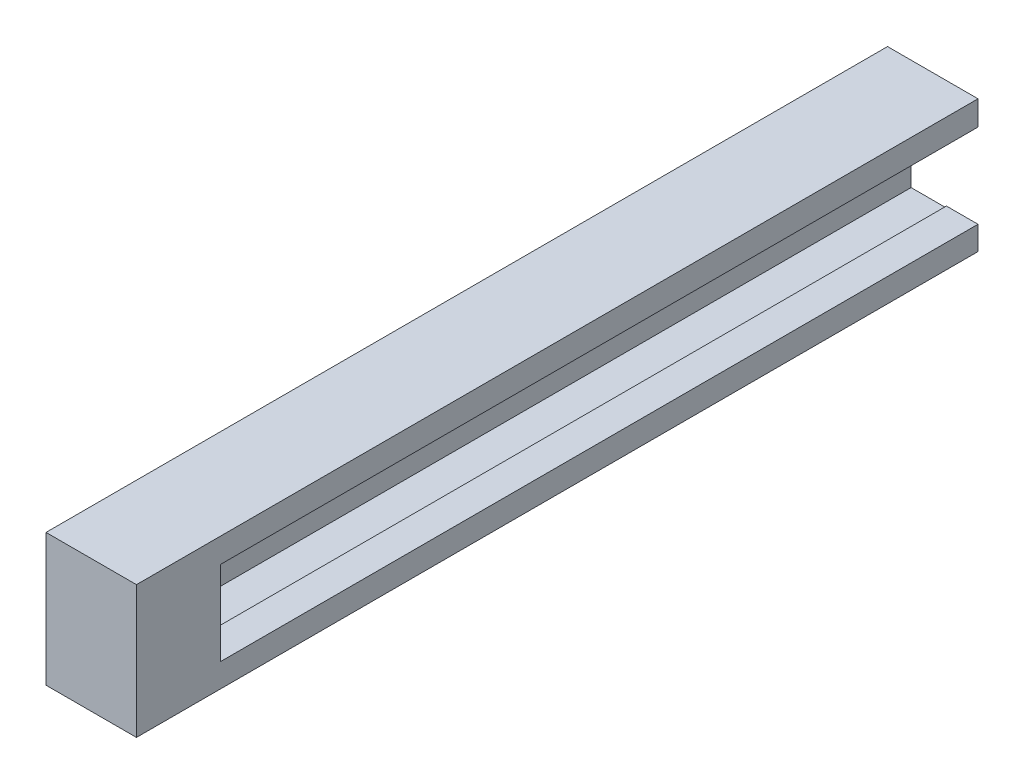
SolidWorks part; units mm, degrees
ref_plane "Front Plane" through (0, 0, 0) normal (0, 0, 1) x (1, 0, 0)
ref_plane "Top Plane" through (0, 0, 0) normal (0, 1, 0) x (1, 0, 0)
ref_plane "Right Plane" through (0, 0, 0) normal (1, 0, 0) x (0, 0, -1)
sketch "Sketch2" plane through (0, 0, 0) normal (0, 0, 1) x (1, 0, 0)
  line L0 (16.75, 6) -> (13, 6) construction
  line L1 (9, 6) -> (13, 6) construction
  line L2 (9, 8.5) -> (9, 6) construction
  line L3 (5, 8.5) -> (9, 8.5) construction
  line L4 (5, 13.5) -> (9, 13.5) construction
  line L5 (9, 16) -> (9, 13.5) construction
  line L6 (9, 16) -> (13, 16) construction
  line L7 (16.75, 16) -> (13, 16) construction
  line L8 (16.75, 6) -> (13, 6)
  line L9 (9, 6) -> (13, 6)
  line L10 (9, 8.5) -> (9, 6)
  line L11 (5, 8.5) -> (9, 8.5)
  line L12 (5, 13.5) -> (9, 13.5)
  line L13 (9, 16) -> (9, 13.5)
  line L14 (9, 16) -> (13, 16)
  line L15 (16.75, 16) -> (13, 16)
  line L16 (16.75, 26) -> (13, 26)
  line L17 (-1, 26) -> (13, 26)
  line L18 (-1, 26) -> (-1, 21.5)
  line L19 (-1, 21.5) -> (-1, 21.5)
  line L20 (5, 13.8) -> (8.7, 13.8)
  line L21 (8.7, 16.3) -> (8.7, 13.8)
  line L22 (8.7, 16.3) -> (13, 16.3)
  line L23 (16.75, 16.3) -> (13, 16.3)
  line L24 (5, 8.3) -> (8.8, 8.3)
  line L25 (8.8, 8.3) -> (8.8, 5.8)
  line L26 (8.8, 5.8) -> (13, 5.8)
  line L27 (16.75, 5.8) -> (13, 5.8)
  line L28 (13, 16.3) -> (13, 16)
  line L29 (13, 5.8) -> (13, 6)
  line L30 (16.75, 5.8) -> (16.75, 6)
  line L31 (16.75, 16.3) -> (16.75, 16)
  line L32 (6, 13.5) -> (6, 13.8)
  line L33 (6, 8.5) -> (6, 8.3)
  line L34 (5, 20) -> (5, 13.5) construction
  line L36 (16.75, 16.3) -> (8.7, 16.3)
  line L37 (16.75, 16.3) -> (16.75, 18.9132)
  line L38 (16.75, 18.9132) -> (8.7, 18.9132)
  line L39 (8.7, 16.3) -> (8.7, 18.9132)
  line L40 (8.7, 18.9132) -> (6, 18.9132)
  line L41 (8.7, 18.9132) -> (8.7, 13.8)
  line L42 (8.7, 13.8) -> (6, 13.8)
  line L43 (6, 18.9132) -> (6, 13.8)
  line L44 (16.75, 5.8) -> (8.8, 5.8)
  line L45 (16.75, 5.8) -> (16.75, 3.1868)
  line L46 (16.75, 3.1868) -> (8.8, 3.1868)
  line L47 (8.8, 5.8) -> (8.8, 3.1868)
  line L48 (8.8, 3.1868) -> (6, 3.1868)
  line L49 (8.8, 3.1868) -> (8.8, 8.3)
  line L50 (8.8, 8.3) -> (6, 8.3)
  line L51 (6, 3.1868) -> (6, 8.3)
  dimension "D4" = 1
  dimension "D1" = 10
  dimension "D2" = 0.3
  dimension "D3" = 0.2
extrude "Boss-Extrude3" add sketch "Sketch2" along normal blind 90 contours L31 L23 L28 L15 | L39 L22 L23 L37 L38 | L40 L43 L20 L21 L39 | L51 L48 L47 L25 L24 | L26 L47 L46 L45 L27 | L27 L30 L8 L29 region at (14.875, 5.9, 0) region at (12.775, 4.4934, 0) region at (7.4, 5.7434, 0) region at (7.35, 16.3566, 0) region at (14.875, 16.15, 0) region at (12.725, 17.6066, 0)
sketch "Sketch3" plane through (0, 0, 90) normal (0, 0, 1) x (1, 0, 0)
  line L0 (6, 8.3) -> (6, 3.1868) construction
  line L1 (6, 3.1868) -> (16.75, 3.1868) construction
  line L2 (16.75, 3.1868) -> (16.75, 6) construction
  line L3 (16.75, 6) -> (13, 6) construction
  line L4 (13, 6) -> (13, 5.8) construction
  line L5 (13, 5.8) -> (8.8, 5.8) construction
  line L6 (8.8, 5.8) -> (8.8, 8.3) construction
  line L7 (8.8, 8.3) -> (6, 8.3) construction
  line L8 (16.75, 16) -> (16.75, 18.9132)
  line L9 (16.75, 18.9132) -> (6, 18.9132)
  line L10 (6, 18.9132) -> (6, 13.8)
  line L11 (6, 13.8) -> (8.7, 13.8)
  line L12 (8.7, 13.8) -> (8.7, 16.3)
  line L13 (8.7, 16.3) -> (13, 16.3)
  line L14 (13, 16.3) -> (13, 16)
  line L15 (13, 16) -> (16.75, 16)
  line L16 (16.75, 16) -> (16.75, 18.9132)
  line L17 (16.75, 18.9132) -> (6, 18.9132)
  line L18 (6, 18.9132) -> (6, 13.8)
  line L19 (6, 13.8) -> (8.7, 13.8)
  line L20 (8.7, 13.8) -> (8.7, 16.3)
  line L21 (8.7, 16.3) -> (13, 16.3)
  line L22 (13, 16.3) -> (13, 16)
  line L23 (13, 16) -> (16.75, 16)
  line L24 (18.5681, 6) -> (18.5681, 16) construction
  line L25 (18.5681, 16) -> (13, 16) construction
  line L26 (13, 16) -> (13, 6) construction
  line L27 (13, 6) -> (18.5681, 6) construction
  line L28 (18.5681, 6) -> (18.5681, 16)
  line L29 (18.5681, 16) -> (13, 16)
  line L30 (13, 16) -> (13, 6)
  line L31 (13, 6) -> (18.5681, 6)
  line L32 (6, 8.3) -> (6, 3.1868)
  line L33 (6, 3.1868) -> (16.75, 3.1868)
  line L34 (16.75, 3.1868) -> (16.75, 6)
  line L35 (16.75, 6) -> (13, 6)
  line L36 (13, 6) -> (13, 5.8)
  line L37 (13, 5.8) -> (8.8, 5.8)
  line L38 (8.8, 5.8) -> (8.8, 8.3)
  line L39 (8.8, 8.3) -> (6, 8.3)
  line L40 (6, 13.8) -> (6, 8.3)
  line L41 (16.75, 16) -> (16.75, 6)
  line M42 (16.75, 16) -> (16.75, 18.9132)
  line M43 (16.75, 18.9132) -> (6, 18.9132)
  line M44 (6, 18.9132) -> (6, 13.8)
  line M45 (6, 13.8) -> (8.7, 13.8)
  line M46 (8.7, 13.8) -> (8.7, 16.3)
  line M47 (8.7, 16.3) -> (13, 16.3)
  line M48 (13, 16.3) -> (13, 16)
  line M49 (13, 16) -> (16.75, 16)
  dimension "D1" = 0
extrude "Boss-Extrude4" add sketch "Sketch3" along normal blind 10 contours L40 L39 L38 L37 L36 L30 M45 M48 M47 M46 | L30 L31 L28 L29 M49 | M49 M42 M43 M44 M45 M46 M47 M48 | L38 L39 L32 L33 L34 L31 L36 L37 region at (10.7291, 17.0813, 90) region at (14.875, 11, 90) region at (9.9889, 11.0667, 90) region at (10.6719, 5.0221, 90)
